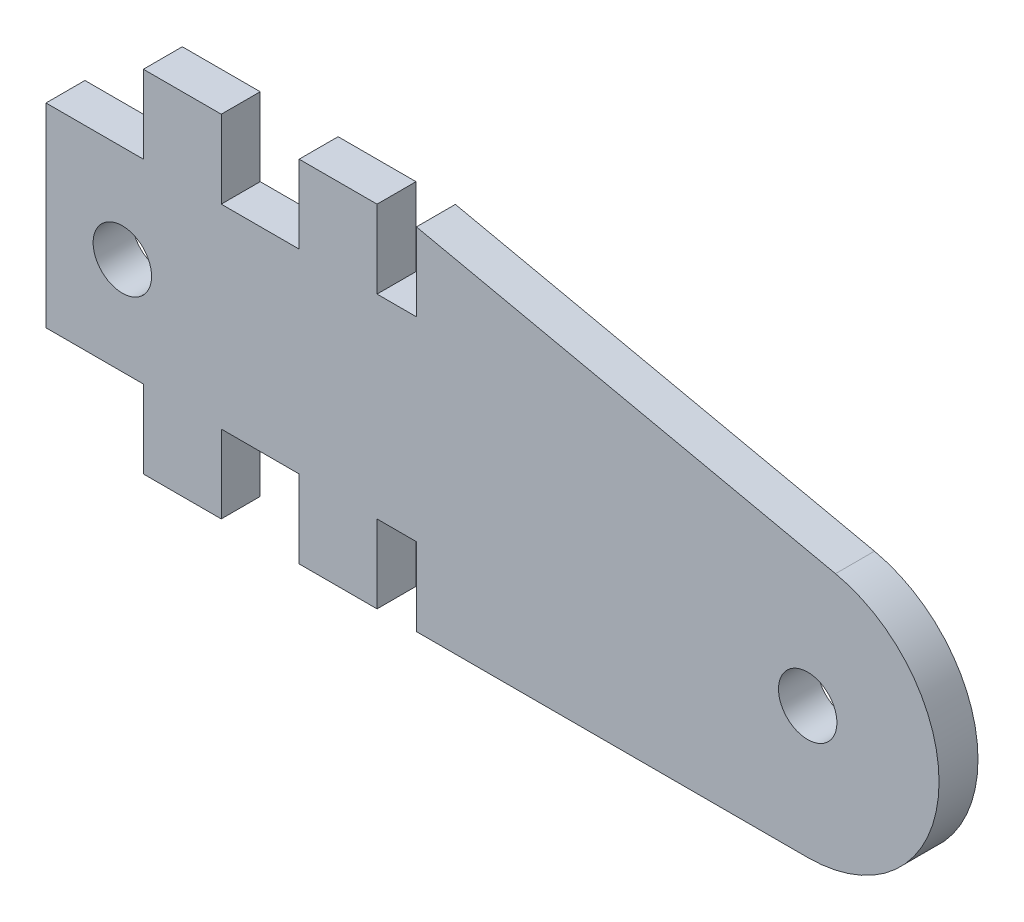
SolidWorks part; units mm, degrees
ref_plane "Front Plane" through (0, 0, 0) normal (0, 0, 1) x (1, 0, 0)
ref_plane "Top Plane" through (0, 0, 0) normal (0, 1, 0) x (1, 0, 0)
ref_plane "Right Plane" through (0, 0, 0) normal (1, 0, 0) x (0, 0, -1)
sketch "Sketch1" plane through (0, 0, 0) normal (0, 0, 1) x (1, 0, 0)
  line L0 (5, 0) -> (9, 0)
  line L1 (5, 4) -> (5, 0)
  line L2 (5, 14) -> (0, 14)
  line L3 (9, 4) -> (13, 4)
  line L4 (13, 4) -> (13, 0)
  line L5 (9, 0) -> (9, 4)
  line L6 (13, 0) -> (17, 0)
  line L7 (17, 0) -> (17, 4)
  line L8 (17, 4) -> (19.0216, 4)
  line L9 (0, 14) -> (0, 4)
  line L10 (19.0216, 4) -> (19.0216, 0)
  line L11 (17, 14) -> (19.0216, 14)
  line L12 (17, 18) -> (17, 14)
  line L13 (13, 18) -> (17, 18)
  line L14 (9, 18) -> (9, 14)
  line L15 (13, 14) -> (13, 18)
  line L16 (9, 14) -> (13, 14)
  line L17 (0, 4) -> (5, 4)
  line L18 (5, 14) -> (5, 18)
  line L19 (5, 18) -> (9, 18)
  line L20 (19.0216, 0) -> (39.1145, 0)
  line L21 (29.045, 0) -> (29.045, -6.4753) construction
  line L22 (19.0216, 14) -> (19.0216, 18)
  line L23 (19.0216, 18) -> (40.5426, 13.3378)
  line L27 (23.6391, 12.0249) -> (21.6695, 11.6776) construction
  line L32 (16.7455, 10.8093) -> (17.6137, 5.8853) construction
  line L33 (16.7455, 10.8093) -> (14.7759, 10.462) construction
  line L34 (14.7759, 10.462) -> (15.6441, 5.538) construction
  line L35 (15.6441, 5.538) -> (17.6137, 5.8853) construction
  line L36 (21.6695, 11.6776) -> (22.5378, 6.7535) construction
  line L37 (22.5378, 6.7535) -> (24.5074, 7.1008) construction
  line L38 (23.6391, 12.0249) -> (24.5074, 7.1008) construction
  arc A0 (39.1145, 0) -> (40.5426, 13.3378) centre (39.1145, 6.7453) ccw
  circle A1 centre (3.9205, 9) radius 1.5
  circle A2 centre (39.1145, 6.7453) radius 12.12 construction
  circle A4 centre (39.1145, 6.7453) radius 1.5
  dimension "D1" = 3
  dimension "D2" = 6.7453
  dimension "D7" = 24.24
  dimension "D3" = 3.9205
  dimension "D4" = 14.7759
  dimension "D5" = 15.6441
  dimension "D6" = 16.7455
  dimension "D8" = 21.6695
  dimension "D16" = 9
  dimension "D12" = 5.538
  dimension "D13" = 5.8853
  dimension "ThumbLinkLengthMCP" = 20.045
  dimension "D9" = 9
  dimension "D10" = 18
  dimension "D11" = 19.0216
extrude "Boss-Extrude1" add sketch "Sketch1" along normal blind 2
equation "\"ThumbLinkLengthMCP@Sketch1\"= \"HB@parametersSketch@prostheticParameters.SLDPRT\" * 0.211"
